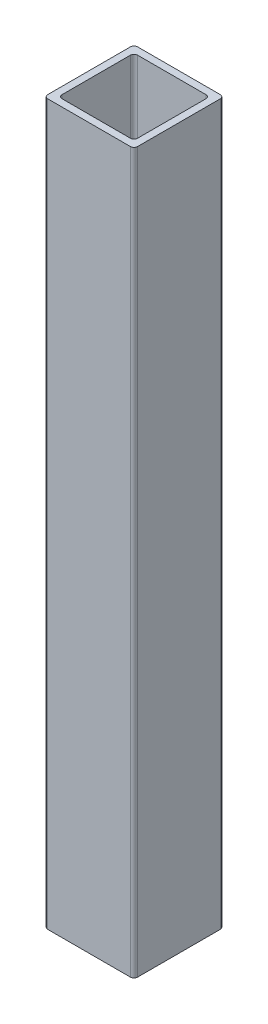
SolidWorks part; units mm, degrees
material "Hexcel AS4C (3000 Filaments)"
ref_plane "Front Plane" through (0, 0, 0) normal (0, 0, 1) x (1, 0, 0)
ref_plane "Top Plane" through (0, 0, 0) normal (0, 1, 0) x (1, 0, 0)
ref_plane "Right Plane" through (0, 0, 0) normal (1, 0, 0) x (0, 0, -1)
sketch "Sketch1" plane through (0, 0, 0) normal (0, 1, 0) x (1, 0, 0)
  line L1 (-11.5, -12.5) -> (11.5, -12.5)
  line L2 (-12.5, -11.5) -> (-12.5, 11.5)
  line L3 (-11.5, 12.5) -> (11.5, 12.5)
  line L4 (12.5, -11.5) -> (12.5, 11.5)
  line L5 (-12.5, -12.5) -> (12.5, 12.5) construction
  line L6 (-12.5, 12.5) -> (12.5, -12.5) construction
  line L7 (-9.5, -10.5) -> (9.5, -10.5)
  line L8 (-10.5, -9.5) -> (-10.5, 9.5)
  line L9 (-9.5, 10.5) -> (9.5, 10.5)
  line L10 (10.5, -9.5) -> (10.5, 9.5)
  line L11 (-10.5, -10.5) -> (10.5, 10.5) construction
  line L12 (-10.5, 10.5) -> (10.5, -10.5) construction
  arc A0 (-11.5, -12.5) -> (-12.5, -11.5) centre (-11.5, -11.5) cw
  arc A1 (11.5, 12.5) -> (12.5, 11.5) centre (11.5, 11.5) cw
  arc A2 (11.5, -12.5) -> (12.5, -11.5) centre (11.5, -11.5) ccw
  arc A3 (-12.5, 11.5) -> (-11.5, 12.5) centre (-11.5, 11.5) cw
  arc A4 (-9.5, -10.5) -> (-10.5, -9.5) centre (-9.5, -9.5) cw
  arc A5 (9.5, -10.5) -> (10.5, -9.5) centre (9.5, -9.5) ccw
  arc A6 (9.5, 10.5) -> (10.5, 9.5) centre (9.5, 9.5) cw
  arc A7 (-10.5, 9.5) -> (-9.5, 10.5) centre (-9.5, 9.5) cw
  point P0 (0, 0)
  point P18 (0, 0)
  dimension "D3" = 1
  dimension "D6" = 1
  dimension "D7" = 1
  dimension "D8" = 1
  dimension "D9" = 1
  dimension "D1" = 25
  dimension "D2" = 25
  dimension "D4" = 21
  dimension "D5" = 21
extrude "Boss-Extrude1" add sketch "Sketch1" along normal blind 200
